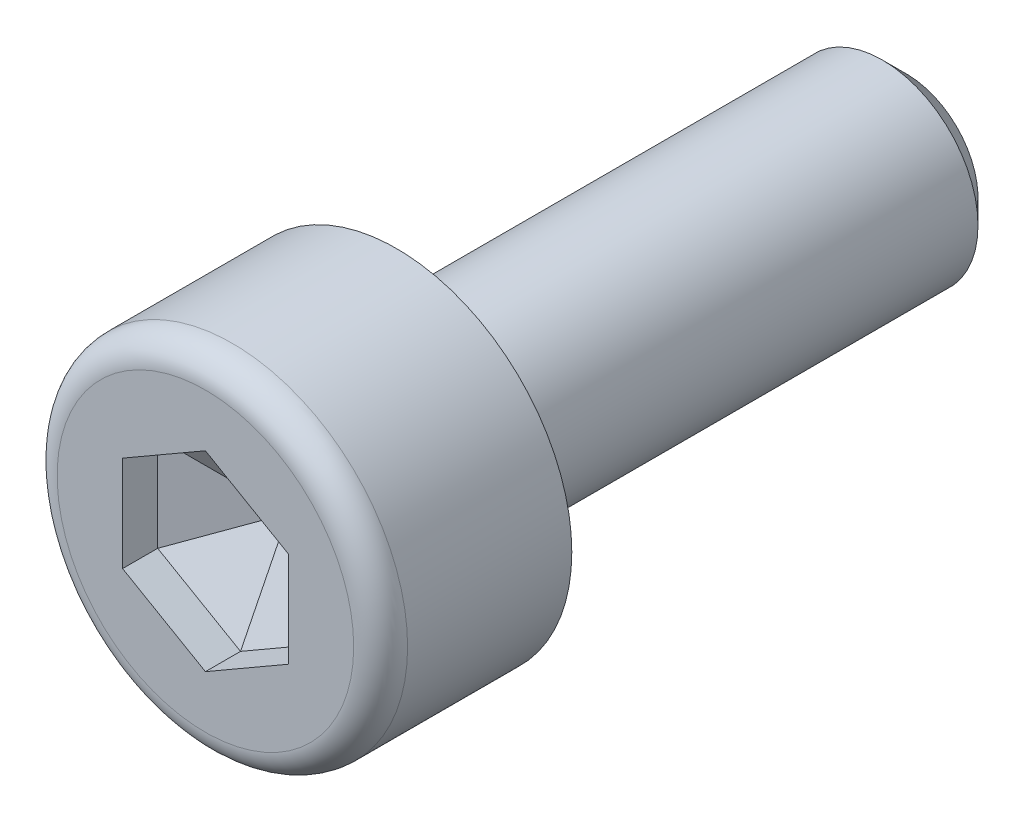
SolidWorks part; units mm, degrees
ref_plane "前视基准面" through (0, 0, 0) normal (0, 0, 1) x (1, 0, 0)
ref_plane "上视基准面" through (0, 0, 0) normal (0, 1, 0) x (1, 0, 0)
ref_plane "右视基准面" through (0, 0, 0) normal (1, 0, 0) x (0, 0, -1)
sketch "草图1" plane through (0, 0, 0) normal (0, 0, 1) x (1, 0, 0)
  circle A0 centre (0, 0) radius 2.75
  dimension "dk" = 5.5
extrude "凸台-拉伸1" add sketch "草图1" along normal blind 3
ref_axis "基准轴1" through (0, 0, 3) along (0, 0, -1)
sketch "草图2" plane through (0, 0, 3) normal (0, 0, 1) x (1, 0, 0)
  line L1 (1.3, 0.7506) -> (0, 1.5011)
  line L2 (0, 1.5011) -> (-1.3, 0.7506)
  line L3 (-1.3, 0.7506) -> (-1.3, -0.7506)
  line L4 (-1.3, -0.7506) -> (0, -1.5011)
  line L5 (0, -1.5011) -> (1.3, -0.7506)
  line L6 (1.3, -0.7506) -> (1.3, 0.7506)
  circle A0 centre (0, 0) radius 1.3 construction
  dimension "s" = 2.6
extrude "切除-拉伸1" cut sketch "草图2" against normal blind 1.3
sketch "草图3" plane through (0, 0, 0) normal (0, 0, -1) x (-1, 0, 0)
  circle A0 centre (0, 0) radius 1.5
  dimension "d" = 3
extrude "凸台-拉伸2" add sketch "草图3" along normal blind 8
cosmetic thread "装饰螺纹线1" parameters "b"=4.9, "D2"=1.221
chamfer "倒角1" distance 0.375 angle 45 1 edges at (-1.5, 0, -8)
fillet "圆角1" radius 0.4231 1 edges at (2.75, 0, 3)
chamfer "倒角2" distance 0.7493 angle 60 6 edges at (-1.3, 0, 1.7) (-0.65, 1.1258, 1.7) (0.65, 1.1258, 1.7) (1.3, 0, 1.7) (-0.65, -1.1258, 1.7) (0.65, -1.1258, 1.7) first distance on face at (-1.3, 0, 2.35) first distance on face at (-0.65, 1.1258, 2.35) first distance on face at (0.65, 1.1258, 2.35) first distance on face at (1.3, 0, 2.35) first distance on face at (-0.65, -1.1258, 2.35) first distance on face at (0.65, -1.1258, 2.35)
fillet "圆角2" radius 0.1 1 edges at (1.5, 0, 0)
ref_plane "基准面1" through (0, 0, 0) normal (0, 0, -1) x (-1, 0, 0)
equation "\"D1@倒角2\" = \"s@草图2\" / 3.47"
equation "\"D1@圆角1\"= \"dk@草图1\" / 13"
equation "\"D1@倒角1\"= \"d@草图3\" / 8"
equation "\"D1@圆角2\"= \"d@草图3\" / \"d@草图3\" * 0.1"
